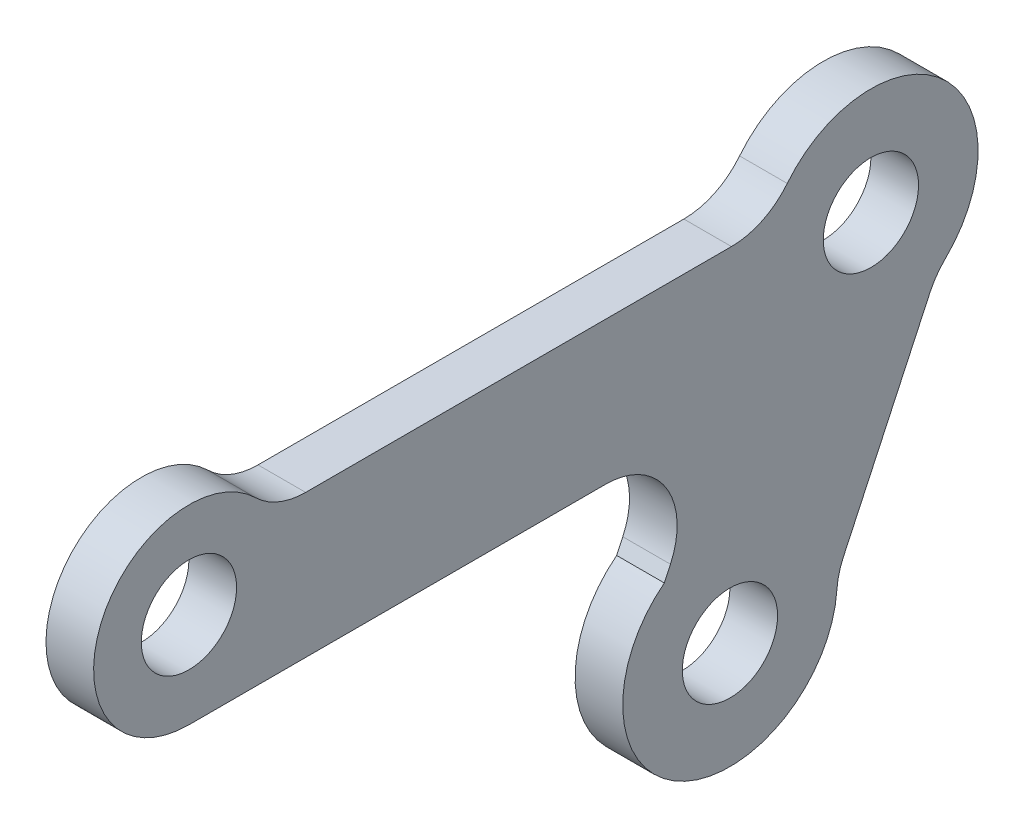
SolidWorks part; units mm, degrees
ref_plane "前视基准面" through (0, 0, 0) normal (0, 0, 1) x (1, 0, 0)
ref_plane "上视基准面" through (0, 0, 0) normal (0, 1, 0) x (1, 0, 0)
ref_plane "右视基准面" through (0, 0, 0) normal (1, 0, 0) x (0, 0, -1)
other "Configuration Table"
sketch "草图1" plane through (0, 0, 0) normal (1, 0, 0) x (0, 0, -1)
  line L1 (-25, 0) -> (0, 0)
  line L2 (-25, 0) -> (-25, -6)
  line L3 (-25, -6) -> (0, -6)
  line L4 (0, 0) -> (0, -6)
  line L5 (0, 0) -> (7.2505, -3.3809)
  line L6 (0, 0) -> (-5.9167, -12.6883)
  line L7 (-5.9167, -12.6883) -> (1.3338, -16.0693)
  line L8 (7.2505, -3.3809) -> (1.3338, -16.0693)
  circle A0 centre (-25, -2) radius 4
  circle A1 centre (3.6252, -1.6905) radius 4.5
  circle A2 centre (-2.2914, -14.3788) radius 4.5
  circle A3 centre (-25, -2) radius 2
  circle A4 centre (3.6252, -1.6905) radius 2
  circle A5 centre (-2.2914, -14.3788) radius 2
  dimension "D5" = 8
  dimension "D6" = 9
  dimension "D7" = 9
  dimension "D9" = 4
  dimension "D1" = 6
  dimension "D2" = 8
  dimension "D3" = 65
  dimension "D4" = 25
  dimension "D8" = 14
extrude "凸台-拉伸1" add sketch "草图1" along normal blind 2 contours A0 | L1 L4 L3 L2 | A1 | L5 L8 L7 L6 | A2
extrude "切除-拉伸1" cut sketch "草图1<3>" along normal through all contours A3 | A4 | A5
sketch "草图1<3>" plane through (0, 0, 0) normal (1, 0, 0) x (0, 0, -1) same geometry as "草图1"
fillet "圆角1" radius 3 5 edges at (1, -14.2009, -2.2051) (1, -5.2493, -6.3792) (1, 0, 0.5452) (1, 0, 21.5359) (1, -6, 2.7978)
